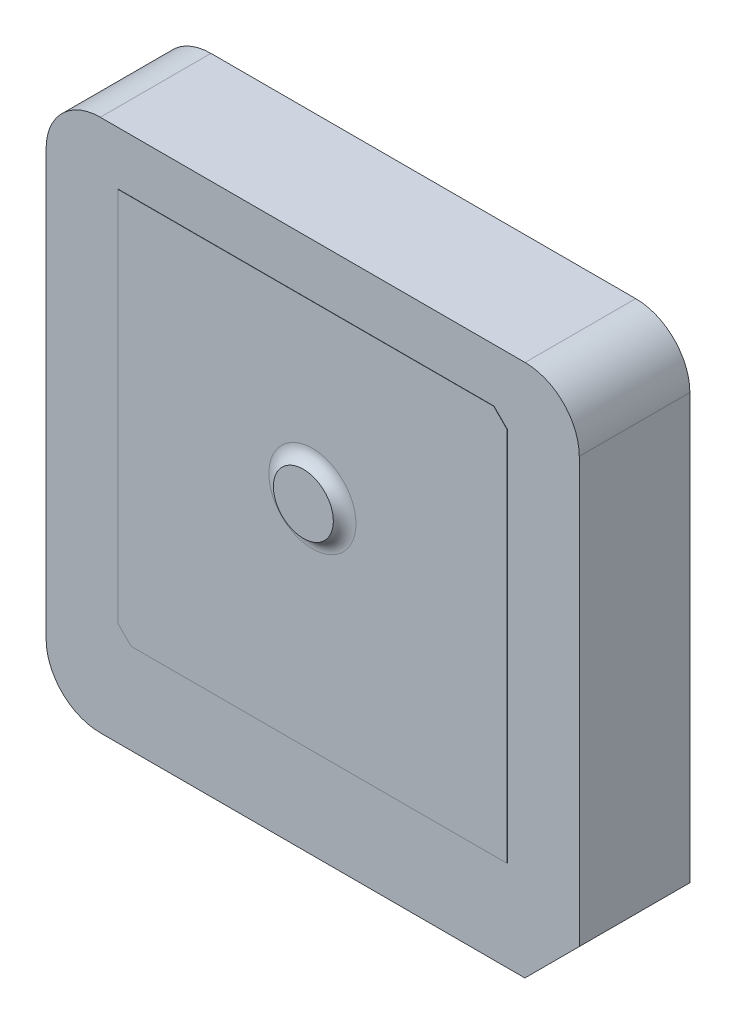
SolidWorks part; units mm, degrees
ref_plane "Front Plane" through (0, 0, 0) normal (0, 0, 1) x (1, 0, 0)
ref_plane "Top Plane" through (0, 0, 0) normal (0, 1, 0) x (1, 0, 0)
ref_plane "Right Plane" through (0, 0, 0) normal (1, 0, 0) x (0, 0, -1)
sketch "Sketch1" plane through (0, 0, 0) normal (0, 0, 1) x (1, 0, 0)
  line L1 (-10, 10) -> (10, 10)
  line L2 (-10, 10) -> (-10, -10)
  line L3 (-10, -10) -> (10, -10)
  line L4 (10, 10) -> (10, -10)
  line L5 (-10, 10) -> (10, -10) construction
  line L6 (-10, -10) -> (10, 10) construction
  point P4 (0, 0)
  point P5 (0, 0)
  point P9 (0, 5.6652)
  point P10 (0, 0)
  point P11 (-10, 10)
  dimension "D1" = 20
extrude "Boss-Extrude1" add sketch "Sketch1" along normal blind 4.15
sketch "Sketch4" plane through (0, 0, 4.15) normal (0, 0, 1) x (1, 0, 0)
  line L0 (-10, -10) -> (10, -10) construction
  line L1 (-10, 10) -> (-10, -10) construction
  circle A0 centre (0, 1.6) radius 1.125
  point P2 (0, 0)
  point P5 (0, -10)
  point P6 (0, 1.512)
  point P9 (-10, 0)
  dimension "D1" = 2.25
  dimension "D2" = 1.6
extrude "Boss-Extrude3" add sketch "Sketch4" along normal blind 0.35
sketch "Sketch5" plane through (0, 0, 4.15) normal (0, 0, 1) x (1, 0, 0)
  line L0 (-10, -10) -> (10, -10) construction
  line L1 (-7.3, 8) -> (7.3, 8)
  line L2 (-7.3, 8) -> (-7.3, -6.6)
  line L3 (-7.3, -6.6) -> (7.3, -6.6)
  line L4 (7.3, 8) -> (7.3, -6.6)
  line L5 (-7.3, 8) -> (7.3, -6.6) construction
  line L6 (-7.3, -6.6) -> (7.3, 8) construction
  point P4 (0, 0.7)
  point P5 (0, 0)
  point P7 (-7.3, -6.4411)
  dimension "D1" = 14.6
  dimension "D2" = 3.4
extrude "Boss-Extrude4" add sketch "Sketch5" along normal blind 0.01
fillet "Fillet1" radius 0.55 1 edges at (1.125, 1.6, 4.16)
chamfer "Chamfer1" distance 0.5 angle 45 2 edges at (7.3, 8, 4.155) (-7.3, -6.6, 4.155)
sketch "Sketch6" plane through (0, 0, 4.15) normal (0, 0, 1) x (1, 0, 0)
  line L1 (-10, -10) -> (10, -10) construction
  line L2 (7.9605, -10) -> (10, -7.9605)
  line L3 (10, -10) -> (10, 10) construction
  line L6 (10, 10) -> (-10, 10) construction
  line L8 (-10, 10) -> (-10, -10) construction
  line L9 (7.9605, -10) -> (10, -10)
  line L10 (10, -10) -> (10, -7.9605)
  line L11 (10, 7.9669) -> (10, 10)
  line L12 (10, 10) -> (7.9669, 10)
  line L13 (-7.9669, 10) -> (-10, 10)
  line L14 (-10, 10) -> (-10, 7.9669)
  line L15 (-10, -7.9669) -> (-10, -10)
  line L16 (-10, -10) -> (-7.9669, -10)
  arc A0 (-10, 7.9669) -> (-7.9669, 10) centre (-7.9669, 7.9669) cw
  arc A1 (7.9669, 10) -> (10, 7.9669) centre (7.9669, 7.9669) cw
  arc A2 (-7.9669, -10) -> (-10, -7.9669) centre (-7.9669, -7.9669) cw
  point P19 (-9.4045, -9.4045)
  point P28 (9.4045, 9.4045)
  point P29 (-9.4045, 9.4045)
  point P30 (8.9803, -8.9803)
  dimension "D1" = 45
  dimension "D2" = 26.6
  dimension "D3" = 26
extrude "Cut-Extrude1" cut sketch "Sketch6" against normal through all
sketch "Sketch7" plane through (0, 0, 0) normal (0, 0, -1) x (-1, 0, 0)
  circle A0 centre (0, 1.6) radius 0.4
  circle A1 centre (0, 1.6) radius 1.125 construction
  point P2 (0, 0)
  point P4 (0, 0)
  dimension "D1" = 0.8
extrude "Boss-Extrude5" add sketch "Sketch7" along normal blind 2
